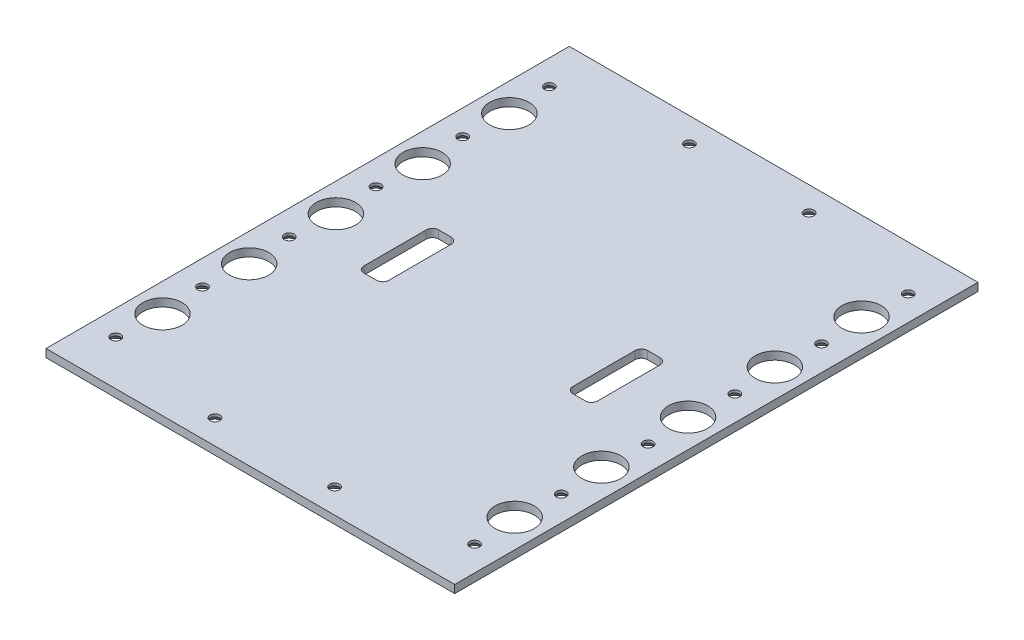
SolidWorks part; units mm, degrees
material "6061-T6 (SS)"
ref_plane "Front Plane" through (0, 0, 0) normal (0, 0, 1) x (1, 0, 0)
ref_plane "Top Plane" through (0, 0, 0) normal (0, 1, 0) x (1, 0, 0)
ref_plane "Right Plane" through (0, 0, 0) normal (1, 0, 0) x (0, 0, -1)
sketch "Sketch1" plane through (0, 0, 0) normal (0, 1, 0) x (1, 0, 0)
  line L1 (-104.14, 133.35) -> (104.14, 133.35)
  line L2 (-104.14, 133.35) -> (-104.14, -133.35)
  line L3 (-104.14, -133.35) -> (104.14, -133.35)
  line L4 (104.14, 133.35) -> (104.14, -133.35)
  line L5 (-104.14, 133.35) -> (104.14, -133.35) construction
  line L6 (-104.14, -133.35) -> (104.14, 133.35) construction
  point P0 (0, 0)
  dimension "D1" = 208.28
  dimension "D2" = 266.7
extrude "Boss-Extrude1" add sketch "Sketch1" along normal blind 4.064
sketch "Sketch2" plane through (0, 4.064, 0) normal (0, 1, 0) x (1, 0, 0)
  line L0 (-104.14, 133.35) -> (-104.14, -133.35) construction
  line L1 (-59.5765, 19.05) -> (-46.8765, 19.05)
  line L2 (-59.5765, 19.05) -> (-59.5765, -19.05)
  line L3 (-59.5765, -19.05) -> (-46.8765, -19.05)
  line L4 (-46.8765, 19.05) -> (-46.8765, -19.05)
  line L5 (-59.5765, 19.05) -> (-46.8765, -19.05) construction
  line L6 (-59.5765, -19.05) -> (-46.8765, 19.05) construction
  point P0 (-53.2265, 0)
  point P7 (0, 0)
  dimension "D1" = 50.9135
  dimension "D2" = 12.7
  dimension "D3" = 38.1
extrude "Cut-Extrude1" cut sketch "Sketch2" against normal through all
mirror "Mirror1" about plane through (0, 0, 0) normal (1, 0, 0) of "Cut-Extrude1"
fillet "Fillet1" radius 3.175 8 edges at (59.5765, 2.032, 19.05) (46.8765, 2.032, 19.05) (59.5765, 2.032, -19.05) (46.8765, 2.032, -19.05) (-46.8765, 2.032, 19.05) (-59.5765, 2.032, 19.05) (-46.8765, 2.032, -19.05) (-59.5765, 2.032, -19.05)
sketch "Sketch3" plane through (0, 0, 0) normal (0, 1, 0) x (1, 0, 0)
  line L0 (-104.14, 133.35) -> (-104.14, -133.35) construction
  line L1 (104.14, 133.35) -> (-104.14, 133.35) construction
  line L2 (-30.48, -120.904) -> (30.48, -120.904) construction
  line L3 (104.14, 0) -> (-104.14, 0) construction
  line L4 (104.14, -133.35) -> (104.14, 133.35) construction
  line L5 (-91.44, 66.294) -> (-89.74, 88.392) construction
  line L6 (-89.74, 88.392) -> (-91.44, 110.49) construction
  line L7 (-104.14, -133.35) -> (104.14, -133.35) construction
  line L8 (-30.48, 120.904) -> (30.48, 120.904) construction
  circle A0 centre (-89.74, 88.392) radius 10
  circle A1 centre (-89.74, 44.196) radius 10
  circle A2 centre (-89.74, 0) radius 10
  circle A3 centre (-89.74, -44.196) radius 10
  circle A9 centre (-91.44, 110.49) radius 6.35 construction
  circle A11 centre (-91.44, -110.49) radius 6.35 construction
  circle A12 centre (-91.44, -66.294) radius 6.35 construction
  circle A13 centre (-91.44, -22.098) radius 6.35 construction
  circle A14 centre (-91.44, 22.098) radius 6.35 construction
  circle A15 centre (-91.44, 66.294) radius 6.35 construction
  circle A16 centre (-89.74, -88.392) radius 10
  point P15 (0, -120.904)
  point P16 (0, 0)
  point P17 (0, 0)
  dimension "D1" = 20
  dimension "D2" = 14.4
  dimension "D3" = 12.446
  dimension "D7" = 12.7
  dimension "D5" = 44.196
  dimension "D6" = 12.7
  dimension "D8" = 22.86
  dimension "D10" = 44.196
  dimension "D11" = 60.96
  dimension "D4" = 5
  dimension "D9" = 5
extrude "Cut-Extrude2" cut sketch "Sketch3" along normal through all
hole_wizard "CSK for #10 Flat Head Machine Screw2" positions "Sketch9" profile "Sketch10" countersink size "#10" standard "ANSI Inch"
sketch "Sketch9" plane through (0, 0, 0) normal (0, -1, 0) x (-1, 0, 0)
  point P0 (91.44, 110.49)
  point P3 (91.44, -110.49)
  point P7 (91.44, -66.294)
  point P10 (91.44, -22.098)
  point P13 (91.44, 22.098)
  point P16 (91.44, 66.294)
  point P19 (30.48, -120.904)
  point P22 (30.48, 120.904)
sketch "Sketch10" plane through (-91.44, 0, -110.49) normal (1, 0, 0) x (0, 0, -1)
  line L0 (0, 0) -> (0, 12.4177)
  line L1 (0, 12.4177) -> (2.4892, 10.922)
  line L2 (2.4892, 10.922) -> (2.4892, 2.7612)
  line L3 (2.4892, 2.7612) -> (4.8895, 0)
  line L5 (4.8895, 0) -> (0, 0)
  line L6 (-2.4892, 2.7612) -> (-4.8895, 0) construction
  line L10 (0, 12.4177) -> (-2.4892, 10.922) construction
  line L11 (0, -6.35) -> (0, 107.95) construction
  dimension "Hole Dia." = 4.9784
  dimension "Hole Depth" = 10.922
  dimension "Near C'Sink Dia." = 9.779
  dimension "Near C'Sink Angle" = 82
  dimension "Drill Angle" = 118
mirror "Mirror2" about plane through (0, 0, 0) normal (1, 0, 0) of "CSK for #10 Flat Head Machine Screw2", "Cut-Extrude2"
